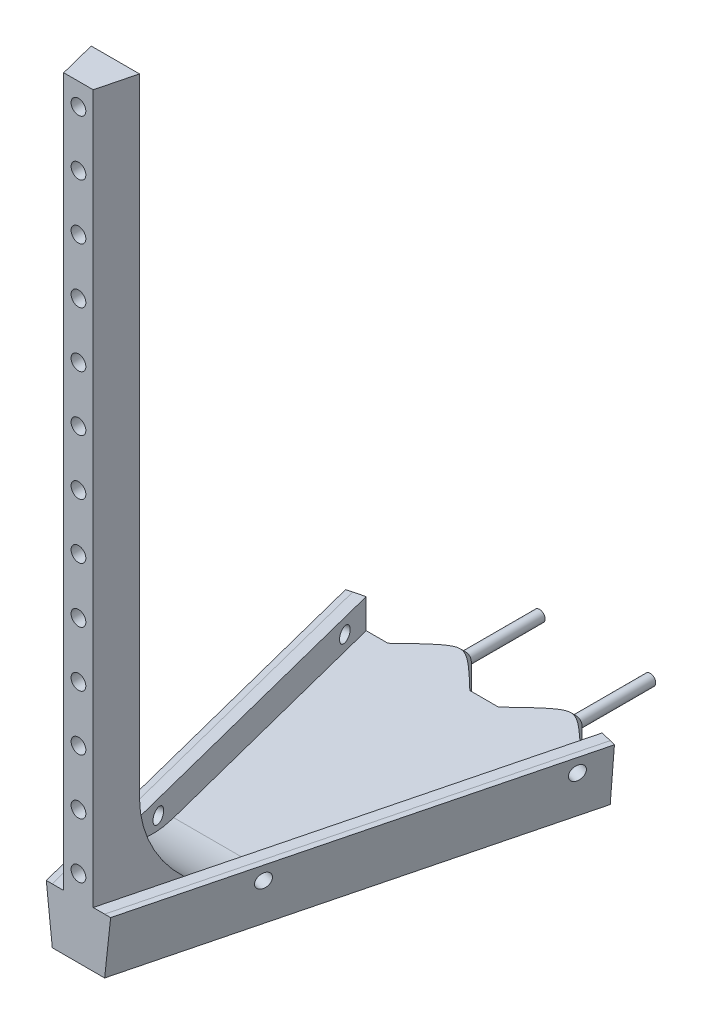
SolidWorks part; units mm, degrees
ref_plane "Plan de face" through (0, 0, 0) normal (0, 0, 1) x (1, 0, 0)
ref_plane "Plan de dessus" through (0, 0, 0) normal (0, 1, 0) x (1, 0, 0)
ref_plane "Plan de droite" through (0, 0, 0) normal (1, 0, 0) x (0, 0, -1)
sketch "Esquisse1" plane through (0, 0, 0) normal (0, 1, 0) x (1, 0, 0)
  line L0 (0, 0) -> (0, 110) construction
  line L1 (-4, 0) -> (4, 0)
  line L2 (-32, 110) -> (32, 110)
  line L3 (-32, 110) -> (-4, 0)
  line L4 (32, 110) -> (4, 0)
  point P6 (0, 0)
  point P9 (0, 110)
  dimension "D1" = 110
  dimension "D2" = 8
  dimension "D3" = 64
extrude "Boss.-Extru.1" add sketch "Esquisse1" against normal blind 7
sketch "Esquisse3" plane through (0, 0, 0) normal (0, 1, 0) x (1, 0, 0)
  line L0 (-6.5455, 10) -> (6.5455, 10)
  line L4 (4, 0) -> (32, 110)
  line L5 (32, 110) -> (-32, 110)
  line L6 (-32, 110) -> (-4, 0)
  line L7 (-4, 0) -> (4, 0)
  line L8 (4, 0) -> (32, 110)
  line L9 (32, 110) -> (-32, 110)
  line L10 (-32, 110) -> (-4, 0)
  line L11 (-4, 0) -> (4, 0)
  line M6 (4, 0) -> (32, 110)
  line M8 (-32, 110) -> (-4, 0)
  line M9 (-4, 0) -> (4, 0)
  dimension "D2" = 10
  dimension "D1" = 0
extrude "Boss.-Extru.3" add sketch "Esquisse3" along normal blind 200 contours L0 M8 M9 M6
sketch "Esquisse4" plane through (0, 0, 0) normal (0, 0, 1) x (1, 0, 0)
  line L0 (0, 200) -> (0, -7) construction
  line L4 (4, -7) -> (4, 200)
  line L5 (4, 200) -> (-4, 200)
  line L6 (-4, 200) -> (-4, -7)
  line L7 (-4, -7) -> (4, -7)
  line L8 (4, -7) -> (4, 200)
  line L9 (4, 200) -> (-4, 200)
  line L10 (-4, 200) -> (-4, -7)
  line L11 (-4, -7) -> (4, -7)
  circle A0 centre (0, 194) radius 2
  dimension "D2" = 4
  dimension "D4" = 6
  dimension "D1" = 0
extrude "Enlèv. mat.-Extru.1" cut sketch "Esquisse4" against normal up to next and the other way through all contours L0 A0 | A0 L0
fillet "Congé1" radius 30 1 edges at (0, 0, -10)
sketch "Esquisse6" plane through (0, 0, -110) normal (0, 0, -1) x (-1, 0, 0)
  line L0 (0, 0) -> (0, -7) construction
  line L4 (32, 0) -> (-32, 0)
  line L5 (-32, 0) -> (-32, -7)
  line L6 (-32, -7) -> (32, -7)
  line L7 (32, 0) -> (-32, 0)
  line L8 (32, -7) -> (32, 0)
  line L9 (-32, 0) -> (-32, -7)
  line L10 (-32, -7) -> (32, -7)
  line L11 (32, -7) -> (32, 0)
  circle A0 centre (-15, -3) radius 1.5
  circle A1 centre (15, -3) radius 1.5
  dimension "D3" = 3
  dimension "D2" = 4
  dimension "D4" = 17
  dimension "D1" = 0
extrude "Boss.-Extru.4" add sketch "Esquisse6" along normal blind 30 contours A0 | A1
chamfer "Chanfrein1" distance 10 angle 45 2 edges at (13.5, -3, -110) (-16.5, -3, -110)
pattern_linear "Répétition linéaire1" count 13 spacing 15 along (0, -1, 0) of "Enlèv. mat.-Extru.1"
ref_plane "Plan1" through (-28.2434, 0, -110.9562) normal (0.2467, 0, 0.9691) x (0, 1, 0)
sketch "Esquisse8" plane through (-28.2434, 0, -110.9562) normal (0.2467, 0, 0.9691) x (0, 1, 0)
  line L0 (-7, 3.8764) -> (0, 3.8764) construction
  line L1 (-7, 3.8764) -> (0, 3.8764)
  line L2 (-7, 6.8764) -> (8, 8.453)
  line L3 (-7, 3.8764) -> (8, 3.8764)
  line L4 (-7, 3.8764) -> (-7, 6.8764)
  line L5 (-7, 6.8764) -> (8, 6.8764)
  line L6 (8, 3.8764) -> (8, 6.8764)
  line L7 (8, 8.453) -> (8, 6.8764)
  line L8 (8, 6.8764) -> (7.9874, 11.5839)
  dimension "D1" = 8
  dimension "D2" = 3
  dimension "D3" = 6
extrude "Boss.-Extru.5" add sketch "Esquisse8" along normal up to surface (113.5077 mm away)
sketch "Esquisse9" plane through (-3.7566, 0, 0.9562) normal (0.9691, 0, -0.2467) x (-0.2467, 0, -0.9691)
  line L0 (114.4944, 4) -> (26.8184, 4) construction
  line L3 (114.4944, 8) -> (21.2158, 8)
  line L4 (42.2622, 0) -> (114.4944, 0)
  line L5 (114.4944, 0) -> (114.4944, 8)
  line L6 (114.4944, 8) -> (21.2158, 8)
  line L7 (42.2622, 0) -> (114.4944, 0)
  line L8 (114.4944, 0) -> (114.4944, 8)
  line L11 (44.4944, 4) -> (-43.1816, 4) construction
  circle A0 centre (106.4944, 4) radius 2
  circle A1 centre (36.4944, 4) radius 2
  ellipse E1 centre (42.2622, 30) end of major axis (73.2189, 30) minor radius 30 (21.2158, 8) -> (42.2622, 0) ccw
  ellipse E2 centre (42.2622, 30) end of major axis (73.2189, 30) minor radius 30 (21.2158, 8) -> (42.2622, 0) ccw
  dimension "D2" = 4
  dimension "D5" = 70
  dimension "D3" = 8
  dimension "D1" = 0
  dimension "D4" = 2
extrude "Enlèv. mat.-Extru.2" cut sketch "Esquisse9" against normal up to next contours A1 | A0
mirror "Symétrie1" about plane through (0, 0, 0) normal (1, 0, 0) of "Boss.-Extru.5", "Enlèv. mat.-Extru.2"
